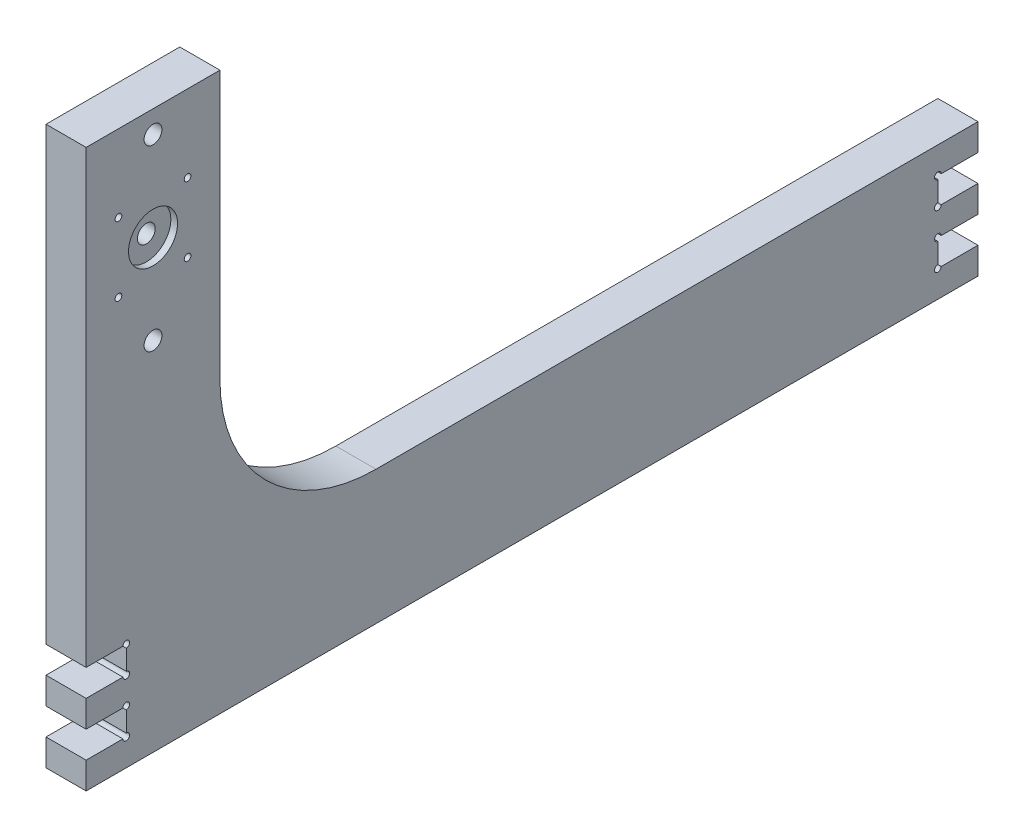
SolidWorks part; units mm, degrees
ref_plane "Front Plane" through (0, 0, 0) normal (0, 0, 1) x (1, 0, 0)
ref_plane "Top Plane" through (0, 0, 0) normal (0, 1, 0) x (1, 0, 0)
ref_plane "Right Plane" through (0, 0, 0) normal (1, 0, 0) x (0, 0, -1)
sketch "Sketch1" plane through (0, 0, 0) normal (1, 0, 0) x (0, 0, -1)
  line L0 (-1000, 0) -> (49000, 0) construction
  line L1 (-30, -250) -> (370, -250)
  line L2 (-30, -250) -> (-30, -238)
  line L4 (370, -250) -> (370, -238)
  line L6 (-30, -202) -> (-13.5, -202) construction
  line L7 (0, -1000) -> (0, 49000) construction
  line L9 (-30, 0) -> (-30, -202)
  line L10 (-30, -214) -> (-13.5, -214) construction
  line L11 (-30, -226) -> (-13.5, -226) construction
  line L12 (-30, -238) -> (-13.5, -238) construction
  line L13 (-12, -203.5) -> (-12, -212.5)
  line L14 (-30, -202) -> (-13.5, -202)
  line L15 (-30, -214) -> (-13.5, -214)
  line L16 (-30, -226) -> (-13.5, -226)
  line L17 (-13.5, -238) -> (-30, -238)
  line L19 (-30, -226) -> (-30, -214)
  line L20 (0, -750) -> (0, 49250) construction
  line L21 (-12, -227.5) -> (-12, -236.5)
  line L22 (353.5, -238) -> (370, -238)
  line L23 (352, -227.5) -> (352, -236.5)
  line L24 (370, -226) -> (353.5, -226)
  line L25 (370, -214) -> (353.5, -214)
  line L26 (352, -203.5) -> (352, -212.5)
  line L27 (370, -202) -> (353.5, -202)
  line L29 (370, -226) -> (370, -214)
  line L30 (370, -190) -> (370, -202)
  line L31 (30, 0) -> (30, -120)
  line L33 (100, -190) -> (370, -190)
  line L34 (-27.1942, -50) -> (27.1942, -50) construction
  line L35 (-30, -214) -> (-30, -226)
  line L36 (-30, -238) -> (-30, -250)
  line L37 (-30, 0) -> (30, 0)
  circle A1 centre (0, -50) radius 4
  circle A2 centre (0, -90) radius 4
  circle A3 centre (0, -10) radius 4
  circle A4 centre (15.5, -34.5) radius 1.5
  arc A5 (100, -190) -> (30, -120) centre (100, -120) cw
  circle A6 centre (-15.5, -34.5) radius 1.5
  circle A7 centre (15.5, -65.5) radius 1.5
  circle A8 centre (-15.5, -65.5) radius 1.5
  arc A9 (-12, -203.5) -> (-13.5, -202) centre (-12, -202) ccw
  arc A10 (-13.5, -214) -> (-12, -212.5) centre (-12, -214) ccw
  arc A11 (-12, -227.5) -> (-13.5, -226) centre (-12, -226) ccw
  arc A12 (-13.5, -238) -> (-12, -236.5) centre (-12, -238) ccw
  arc A13 (353.5, -202) -> (352, -203.5) centre (352, -202) ccw
  arc A14 (352, -212.5) -> (353.5, -214) centre (352, -214) ccw
  arc A15 (353.5, -226) -> (352, -227.5) centre (352, -226) ccw
  arc A16 (352, -236.5) -> (353.5, -238) centre (352, -238) ccw
  point P0 (0, 0)
  point P11 (370, -244)
  point P51 (0, -50)
  point P62 (0, 0)
  dimension "D7" = 48
  dimension "D14" = 8
  dimension "D16" = 50
  dimension "D18" = 3
  dimension "D10" = 70
  dimension "D23" = 3
  dimension "D29" = 3
  dimension "D3" = 18
  dimension "D4" = 60
  dimension "D5" = 12
  dimension "D6" = 400
  dimension "D8" = 250
  dimension "D9" = 60
  dimension "D11" = 18
  dimension "D13" = 70
  dimension "D15" = 10
  dimension "D17" = 40
  dimension "D19" = 15.5
  dimension "D20" = 15.5
  dimension "D21" = 100
  dimension "D22" = 120
  dimension "D25" = 18
  dimension "D26" = 12
  dimension "D27" = 36
  dimension "D28" = 9
  dimension "D24" = 4
  dimension "D30" = 4
extrude "Boss-Extrude1" add sketch "Sketch1" along normal blind 18
sketch "Sketch3" plane through (18, 0, 0) normal (1, 0, 0) x (0, 0, -1)
  circle A0 centre (0, -50) radius 11
  dimension "D1" = 22
extrude "Cut-Extrude1" cut sketch "Sketch3" against normal blind 3
sketch "Sketch4" plane through (18, 0, 0) normal (1, 0, 0) x (0, 0, -1)
  line L0 (370, -202) -> (352, -202)
  line L1 (352, -202) -> (352, -214)
  line L3 (370, -214) -> (352, -214)
  line L4 (370, -226) -> (352, -226)
  line L5 (370, -238) -> (352, -238)
  line L6 (352, -236.5) -> (352, -238)
  line L7 (352, -226) -> (352, -227.5)
  line L8 (170, -1250) -> (170, 48750) construction
  line L9 (-30, -250) -> (370, -250) construction
  line L10 (-12, -226) -> (-12, -227.5)
  line L11 (-12, -236.5) -> (-12, -238)
  line L12 (-30, -238) -> (-12, -238)
  line L13 (-30, -226) -> (-12, -226)
  line L14 (-30, -214) -> (-12, -214)
  line L15 (-12, -202) -> (-12, -214)
  line L16 (-30, -202) -> (-12, -202)
  arc A0 (353.5, -202) -> (352, -203.5) centre (352, -202) ccw
  arc A1 (352, -212.5) -> (353.5, -214) centre (352, -214) ccw
  arc A2 (353.5, -226) -> (352, -227.5) centre (352, -226) ccw
  arc A3 (352, -236.5) -> (353.5, -238) centre (352, -238) ccw
  arc A4 (-12, -236.5) -> (-13.5, -238) centre (-12, -238) cw
  arc A5 (-13.5, -226) -> (-12, -227.5) centre (-12, -226) cw
  arc A6 (-12, -212.5) -> (-13.5, -214) centre (-12, -214) cw
  arc A7 (-13.5, -202) -> (-12, -203.5) centre (-12, -202) cw
  point P26 (170, -250)
  point P42 (0, 0)
  point P43 (0, 0)
  point P44 (0, 0)
  dimension "D1" = 3
  dimension "D3" = 12
  dimension "D2" = 4
  dimension "D4" = 3
